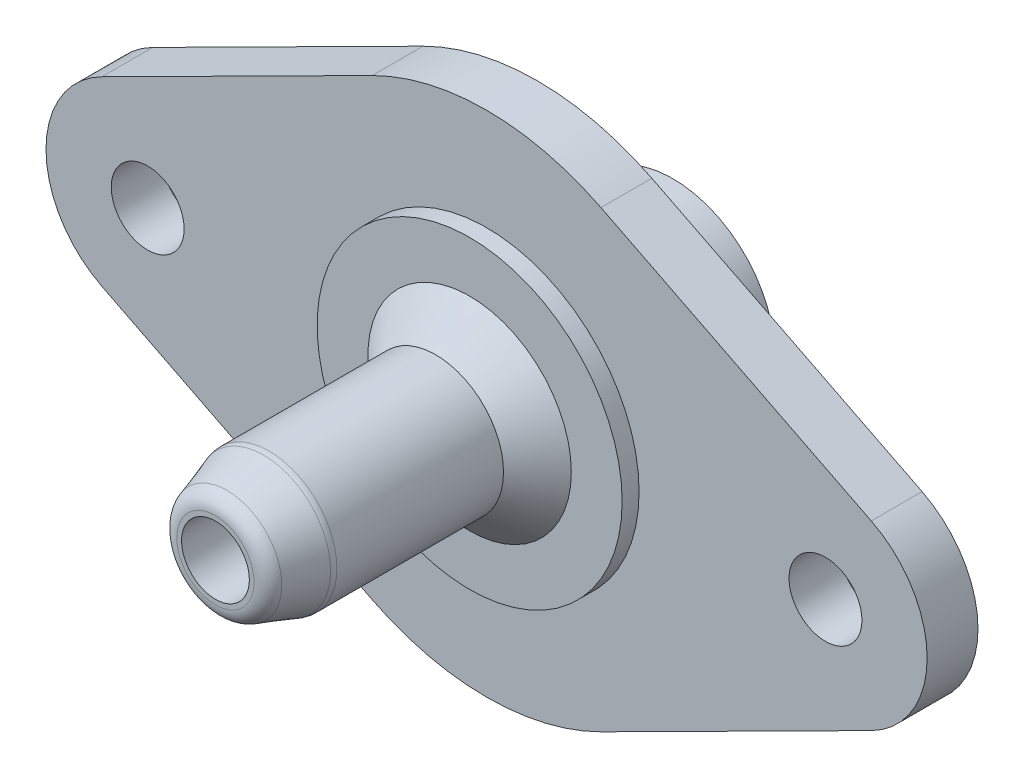
SolidWorks part; units mm, degrees
ref_plane "前视基准面" through (0, 0, 0) normal (0, 0, 1) x (1, 0, 0)
ref_plane "上视基准面" through (0, 0, 0) normal (0, 1, 0) x (1, 0, 0)
ref_plane "右视基准面" through (0, 0, 0) normal (1, 0, 0) x (0, 0, -1)
sketch "草图1" plane through (0, 0, 0) normal (0, 0, 1) x (1, 0, 0)
  circle A0 centre (0, 0) radius 6
  circle A1 centre (0, 0) radius 3
  dimension "D1" = 12
  dimension "D2" = 6
extrude "凸台-拉伸1" add sketch "草图1" along normal blind 8
sketch "草图2" plane through (0, 0, 8) normal (0, 0, 1) x (1, 0, 0)
  circle A0 centre (0, 0) radius 9
  circle A1 centre (0, 0) radius 3 construction
  circle A2 centre (0, 0) radius 3
  dimension "D1" = 18
extrude "凸台-拉伸2" add sketch "草图2" along normal blind 4
sketch "草图3" plane through (0, 0, 12) normal (0, 0, 1) x (1, 0, 0)
  circle A0 centre (0, 0) radius 2
  circle A1 centre (0, 0) radius 4
  dimension "D1" = 4
  dimension "D2" = 8
extrude "凸台-拉伸3" add sketch "草图3" along normal blind 15
chamfer "倒角1" distance 2 angle 45 2 edges at (2, 0, 12) (4, 0, 12)
chamfer "倒角2" distance 3 distance2 1 1 edges at (4, 0, 27) first distance on face at (4, 0, 14)
fillet "圆角1" radius 1 2 edges at (3, 0, 27) (4, 0, 24)
sketch "草图4" plane through (0, 0, 8) normal (0, 0, 1) x (1, 0, 0)
  line L0 (-22.7, 5.3582) -> (-6.75, 13.3954)
  line L1 (-22.7, -5.3582) -> (-6.75, -13.3954)
  line L2 (6.75, 13.3954) -> (22.7, 5.3582)
  line L3 (22.7, -5.3582) -> (6.75, -13.3954)
  circle A0 centre (0, 0) radius 9 construction
  circle A1 centre (0, 0) radius 9
  arc A2 (-6.75, -13.3954) -> (6.75, -13.3954) centre (0, 0) ccw
  circle A3 centre (20, 0) radius 2.15
  circle A4 centre (-20, 0) radius 2.15
  arc A5 (-22.7, 5.3582) -> (-22.7, -5.3582) centre (-20, 0) ccw
  arc A6 (22.7, -5.3582) -> (22.7, 5.3582) centre (20, 0) ccw
  arc A7 (6.75, 13.3954) -> (-6.75, 13.3954) centre (0, 0) ccw
  dimension "D3" = 30
  dimension "D4" = 4.3
  dimension "D5" = 12
  dimension "D1" = 20
  dimension "D2" = 20
extrude "凸台-拉伸5" add sketch "草图4" along normal blind 3
